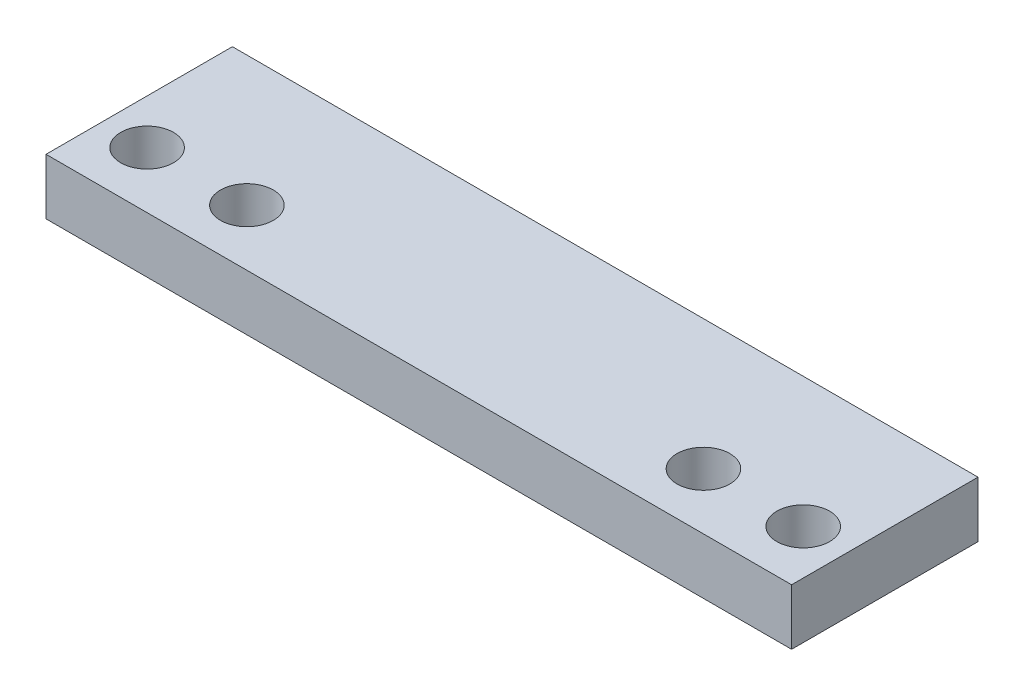
SolidWorks part; units mm, degrees
material "AISI Type A2 Tool Steel"
ref_plane "Front Plane" through (0, 0, 0) normal (0, 0, 1) x (1, 0, 0)
ref_plane "Top Plane" through (0, 0, 0) normal (0, 1, 0) x (1, 0, 0)
ref_plane "Right Plane" through (0, 0, 0) normal (1, 0, 0) x (0, 0, -1)
other "Bounding Box"
ref_plane "Default Plane" through (0, 2.286, 19.05) normal (0, -1, 0) x (-1, 0, 0)
sketch "Sketch1" plane through (0, 0, 0) normal (0, 1, 0) x (1, 0, 0)
  line L0 (-31.75, -3.1369) -> (-27.94, -3.1369) construction
  line L1 (-31.75, -7.9375) -> (31.75, -7.9375)
  line L2 (-31.75, -7.9375) -> (-31.75, 7.9375)
  line L3 (-31.75, 7.9375) -> (31.75, 7.9375)
  line L4 (31.75, -7.9375) -> (31.75, 7.9375)
  line L5 (-31.75, -7.9375) -> (31.75, 7.9375) construction
  line L6 (-31.75, 7.9375) -> (31.75, -7.9375) construction
  line L7 (-27.94, -3.1369) -> (-19.4412, -3.1369) construction
  line L8 (-19.4412, -3.1369) -> (-19.4412, -7.9375) construction
  line L9 (0, 0) -> (0, 7.9375) construction
  circle A0 centre (-27.94, -3.1369) radius 2.2479
  circle A1 centre (-19.4412, -3.1369) radius 2.2479
  circle A2 centre (27.94, -3.1369) radius 2.2479
  circle A3 centre (19.4412, -3.1369) radius 2.2479
  point P0 (0, 0)
  dimension "D3" = 4.4958
  dimension "D1" = 63.5
  dimension "D2" = 15.875
  dimension "D4" = 4.8006
  dimension "D5" = 3.81
  dimension "D6" = 8.4988
extrude "Boss-Extrude1" add sketch "Sketch1" along normal mid plane 4.7625
equation "\"Unit Measure\"= \"BoundingVolume\" / \"Thickness\"'in^2"
